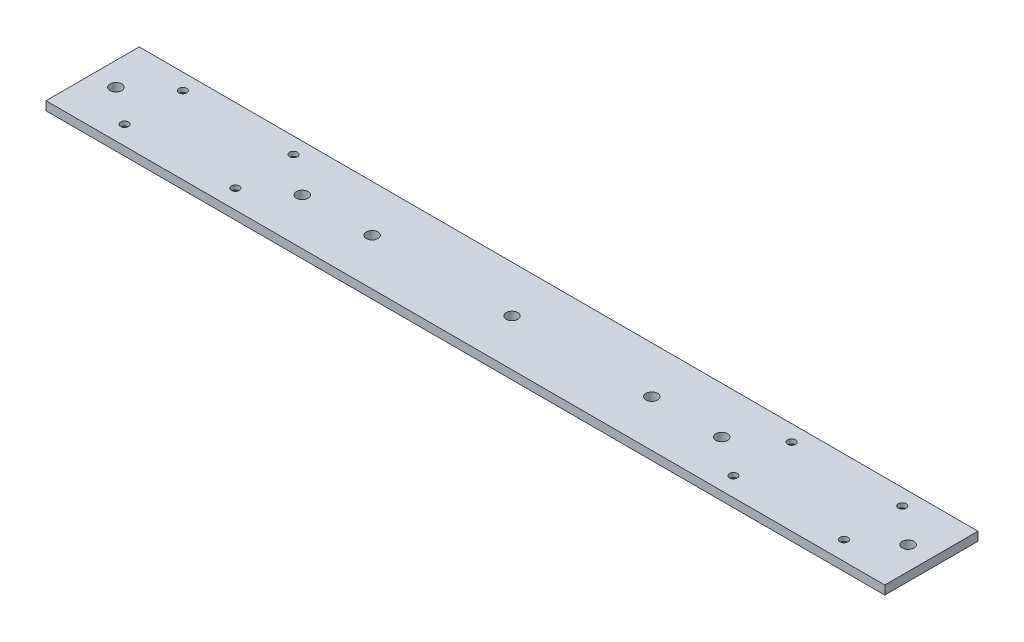
SolidWorks part; units mm, degrees
material "6061 Alloy"
ref_plane "Front Plane" through (0, 0, 0) normal (0, 0, 1) x (1, 0, 0)
ref_plane "Top Plane" through (0, 0, 0) normal (0, 1, 0) x (1, 0, 0)
ref_plane "Right Plane" through (0, 0, 0) normal (1, 0, 0) x (0, 0, -1)
sketch "Sketch1" plane through (0, 0, 0) normal (0, 1, 0) x (1, 0, 0)
  line L1 (0, 0) -> (457.2, 0)
  line L2 (0, 0) -> (0, 50.8)
  line L3 (0, 50.8) -> (457.2, 50.8)
  line L4 (457.2, 0) -> (457.2, 50.8)
  dimension "D1" = 457.2
  dimension "D2" = 50.8
extrude "Boss-Extrude1" add sketch "Sketch1" along normal blind 4.7625
sketch "Sketch2" plane through (0, 4.7625, 0) normal (0, 1, 0) x (1, 0, 0)
  line L0 (0, 0) -> (457.2, 0) construction
  line L1 (0, 50.8) -> (0, 0) construction
  circle A0 centre (12.7, 25.4) radius 3.175
  circle A1 centre (444.5, 25.4) radius 3.175
  dimension "D1" = 25.4
  dimension "D2" = 25.4
  dimension "D3" = 12.7
  dimension "D4" = 444.5
extrude "Cut-Extrude1" cut sketch "Sketch2" against normal blind 244.602
sketch "Sketch3" plane through (0, 4.7625, 0) normal (0, 1, 0) x (1, 0, 0)
  line L0 (457.2, 50.8) -> (0, 50.8) construction
  line L1 (457.2, 0) -> (457.2, 50.8) construction
  circle A0 centre (152.4, 25.4) radius 3.175
  circle A1 centre (304.8, 25.4) radius 3.175
  circle A2 centre (228.6, 25.4) radius 3.175
  dimension "D1" = 25.4
  dimension "D2" = 25.4
  dimension "D3" = 25.4
  dimension "D4" = 76.2
  dimension "D5" = 228.6
  dimension "D6" = 76.2
extrude "Cut-Extrude2" cut sketch "Sketch3" against normal blind 244.602
sketch "Sketch4" plane through (0, 4.7625, 0) normal (0, 1, 0) x (1, 0, 0)
  line L0 (457.2, 50.8) -> (0, 50.8) construction
  line L1 (0, 50.8) -> (0, 0) construction
  line L2 (457.2, 0) -> (457.2, 50.8) construction
  circle A0 centre (114.3, 25.4) radius 3.175
  circle A1 centre (342.9, 25.4) radius 3.175
  dimension "D1" = 25.4
  dimension "D4" = 114.3
  dimension "D2" = 25.4
  dimension "D3" = 114.3
extrude "Cut-Extrude4" cut sketch "Sketch4" against normal blind 103.378
hole_wizard "CSK for #8 Flat Head Machine Screw1" positions "Sketch8" profile "Sketch7" countersink size "#8" standard "ANSI Inch" end condition through all
sketch "Sketch8" plane through (0, 0, 0) normal (0, -1, 0) x (-1, 0, 0)
  point P0 (-424.6625, 42.0688)
  point P3 (-424.6625, 10.3188)
  point P6 (-364.3375, 10.3188)
  point P9 (-364.3375, 42.0688)
  point P12 (-92.8625, 42.0688)
  point P15 (-92.8625, 10.3188)
  point P18 (-32.5375, 10.3188)
  point P21 (-32.5375, 42.0688)
sketch "Sketch7" plane through (424.6625, 0, -42.0688) normal (1, 0, 0) x (0, 0, -1)
  line L0 (0, 0) -> (0, 4.7625)
  line L1 (0, 4.7625) -> (2.1526, 4.7625)
  line L2 (2.1526, 4.7625) -> (2.1526, 2.3741)
  line L3 (2.1526, 2.3741) -> (4.2164, 0)
  line L5 (4.2164, 0) -> (0, 0)
  line L6 (-2.1527, 2.3741) -> (-4.2164, 0) construction
  line L11 (0, -6.35) -> (0, 107.95) construction
  dimension "Thru Hole Dia." = 4.3053
  dimension "Thru Hole Depth" = 4.7625
  dimension "Near C'Sink Dia." = 8.4328
  dimension "Near C'Sink Angle" = 82
